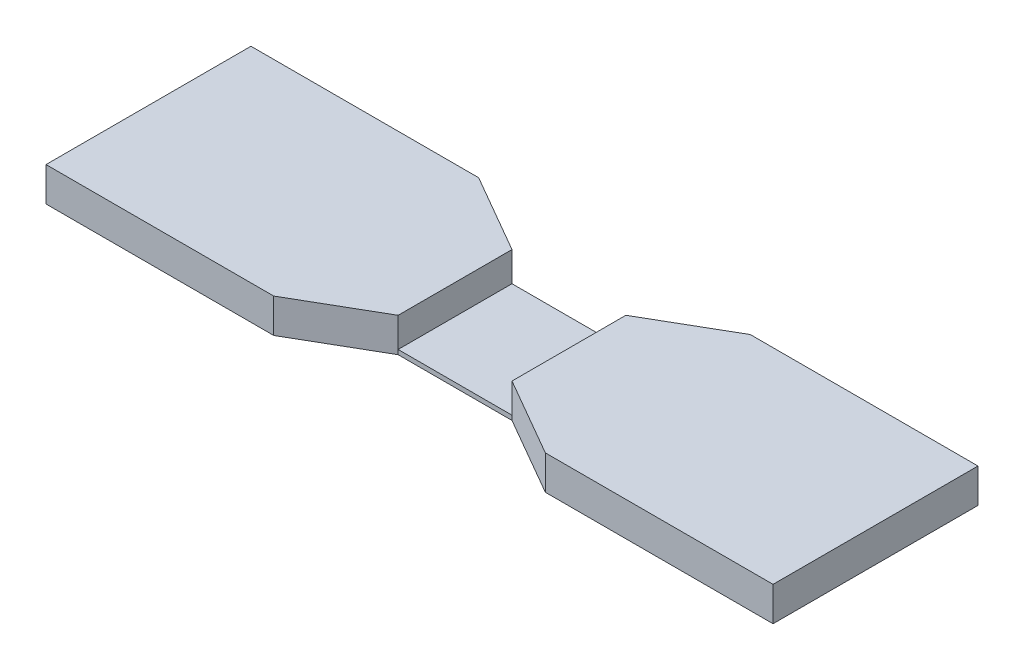
SolidWorks part; units mm, degrees
ref_plane "Front Plane" through (0, 0, 0) normal (0, 0, 1) x (1, 0, 0)
ref_plane "Top Plane" through (0, 0, 0) normal (0, 1, 0) x (1, 0, 0)
ref_plane "Right Plane" through (0, 0, 0) normal (1, 0, 0) x (0, 0, -1)
sketch "Sketch1" plane through (0, 0, 0) normal (0, 1, 0) x (1, 0, 0)
  line L0 (0, 5.0297) -> (-10, 5.0297)
  line L1 (0, 5.0297) -> (6.9282, 9.0297)
  line L2 (6.9282, 9.0297) -> (26.9282, 9.0297)
  line L3 (26.9282, 9.0297) -> (26.9282, -8.9703)
  line L6 (-5, 5.0297) -> (-5, -4.9703) construction
  line L8 (-36.9282, 0.0297) -> (26.9282, 0.0297) construction
  line L9 (6.9282, -8.9703) -> (26.9282, -8.9703)
  line L10 (0, -4.9703) -> (6.9282, -8.9703)
  line L11 (0, -4.9703) -> (-10, -4.9703)
  line L12 (-10, -4.9703) -> (-16.9282, -8.9703)
  line L13 (-16.9282, -8.9703) -> (-36.9282, -8.9703)
  line L14 (-36.9282, 9.0297) -> (-36.9282, -8.9703)
  line L15 (-16.9282, 9.0297) -> (-36.9282, 9.0297)
  line L16 (-10, 5.0297) -> (-16.9282, 9.0297)
  line L17 (-10, 5.0297) -> (-10, -4.9703)
  line L18 (0, 5.0297) -> (0, -4.9703)
  point P4 (0, 0)
  point P14 (-5, 0.0297)
  point P20 (-10, 0)
  dimension "D2" = 5
  dimension "D3" = 20
  dimension "D4" = 150
  dimension "D6" = 8
extrude "Boss-Extrude1" add sketch "Sketch1" along normal blind 3 contours L17 L16 L15 L14 L13 L12 | L1 L18 L10 L9 L3 L2 region at (14.1405, 0, -0.0297) region at (-24.1405, 0, -0.0297)
extrude "Boss-Extrude2" add sketch "Sketch1<3>" along normal blind 0.4 contours L18 L0 L17 L11 region at (-5, 0, -0.0297)
sketch "Sketch1<3>" plane through (0, 0, 0) normal (0, 1, 0) x (1, 0, 0) same geometry as "Sketch1"
